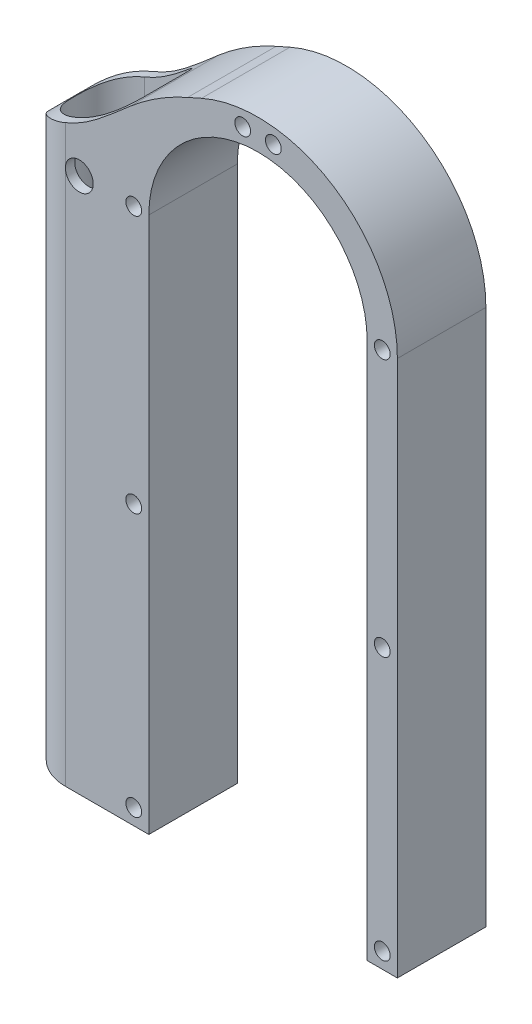
SolidWorks part; units mm, degrees
ref_plane "Front Plane" through (0, 0, 0) normal (0, 0, 1) x (1, 0, 0)
ref_plane "Top Plane" through (0, 0, 0) normal (0, 1, 0) x (1, 0, 0)
ref_plane "Right Plane" through (0, 0, 0) normal (1, 0, 0) x (0, 0, -1)
sketch "Sketch1" plane through (0, 0, 0) normal (0, 0, 1) x (1, 0, 0)
  line L0 (-179.0854, -18.7892) -> (-179.0854, 212.1883)
  line L1 (-119.0854, -18.7892) -> (-119.0854, 212.1883)
  line L2 (-172.5854, -18.7892) -> (-172.5854, 212.1883)
  line L3 (-125.5854, -18.7892) -> (-125.5854, 212.1883)
  arc A0 (-119.0854, 212.1883) -> (-179.0854, 212.1883) centre (-149.0854, 212.1883) ccw
  arc A1 (-179.0854, -18.7892) -> (-119.0854, -18.7892) centre (-149.0854, -18.7892) ccw
  arc A2 (-125.5854, 212.1883) -> (-172.5854, 212.1883) centre (-149.0854, 212.1883) ccw
  arc A3 (-172.5854, -18.7892) -> (-125.5854, -18.7892) centre (-149.0854, -18.7892) ccw
  dimension "D1" = 47
  dimension "D2" = 47
  dimension "D3" = 53.5
extrude "Boss-Extrude1" add sketch "Sketch1" along normal blind 19.05
sketch "Sketch2" plane through (0, 0, 19.05) normal (0, 0, 1) x (1, 0, 0)
  line L0 (-175.8354, 212.1883) -> (-175.8354, -18.7892) construction
  line L1 (-122.3354, 212.1883) -> (-122.3354, -18.7892) construction
  line L2 (-149.0854, 242.1883) -> (-149.0854, 231.9427) construction
  line L3 (-149.0854, -48.7892) -> (-149.0854, -37.4384) construction
  line L4 (-179.0854, 96.6996) -> (-118.7003, 96.6996) construction
  line L5 (-179.0854, 212.1883) -> (-179.0854, -18.7892) construction
  arc A0 (-122.3354, 212.1883) -> (-175.8354, 212.1883) centre (-149.0854, 212.1883) ccw construction
  arc A1 (-119.0854, 212.1883) -> (-179.0854, 212.1883) centre (-149.0854, 212.1883) ccw construction
  arc A2 (-125.5854, 212.1883) -> (-172.5854, 212.1883) centre (-149.0854, 212.1883) ccw construction
  arc A3 (-175.8354, -18.7892) -> (-122.3354, -18.7892) centre (-149.0854, -18.7892) ccw construction
  arc A4 (-179.0854, -18.7892) -> (-119.0854, -18.7892) centre (-149.0854, -18.7892) ccw construction
  circle A5 centre (-145.7854, 238.734) radius 1.7
  circle A7 centre (-122.3354, 212.1883) radius 1.7
  circle A8 centre (-152.4854, -45.3222) radius 1.7
  circle A9 centre (-168.0005, -37.7043) radius 1.7
  circle A10 centre (-175.8354, -18.7892) radius 1.7
  circle A11 centre (-175.8354, 212.1883) radius 1.7
  circle A13 centre (-145.6854, -45.3222) radius 1.7
  circle A14 centre (-175.8354, 100.0996) radius 1.7
  circle A15 centre (-175.8354, 93.2996) radius 1.7
  circle A16 centre (-122.3354, 100.0996) radius 1.7
  circle A17 centre (-122.3354, 93.2996) radius 1.7
  circle A19 centre (-122.3354, -18.7892) radius 1.7
  circle A20 centre (-130.1703, -37.7043) radius 1.7
  circle A25 centre (-175.8354, 156.6996) radius 1.7
  circle A26 centre (-122.3354, 156.6996) radius 1.7
  circle A29 centre (-175.8354, 66.6996) radius 1.7
  circle A30 centre (-122.3354, 66.6996) radius 1.7
  circle A31 centre (-175.8354, 36.6996) radius 1.7
  circle A32 centre (-122.3354, 36.6996) radius 1.7
  circle A33 centre (-175.8354, 6.6996) radius 1.7
  circle A34 centre (-122.3354, 6.6996) radius 1.7
  circle A35 centre (-152.3854, 238.734) radius 1.7
  point P35 (-149.0854, 212.1883)
  point P52 (-149.0854, -18.7892)
  dimension "D1" = 3.25
  dimension "D2" = 3.25
  dimension "D3" = 3.25
  dimension "D4" = 3.4
  dimension "D6" = 3.4
  dimension "D8" = 3.4
  dimension "D9" = 3.4
  dimension "D5" = 3.4
  dimension "D12" = 3.3
  dimension "D13" = 3.3
  dimension "D14" = 3.4
  dimension "D7" = 3.4
  dimension "D16" = 3.4
  dimension "D17" = 3.4
  dimension "D18" = 3.4
  dimension "D19" = 3.4
  dimension "D20" = 3.4
  dimension "D10" = 3.4
  dimension "D11" = 3.4
  dimension "D21" = 3.4
  dimension "D22" = 3.4
  dimension "D25" = 3.4
  dimension "D26" = 3.4
  dimension "D15" = 3.4
  dimension "D23" = 3.4
extrude "Cut-Extrude1" cut sketch "Sketch2" against normal through all
sketch "Sketch3" plane through (0, 0, 19.05) normal (0, 0, 1) x (1, 0, 0)
  line L1 (-149.0854, 96.6996) -> (-100.1673, 96.6996)
  line L2 (-100.1673, 96.6996) -> (-100.1673, -59.1719)
  line L3 (-100.1673, -59.1719) -> (-212.5278, -59.1719)
  line L4 (-212.5278, -59.1719) -> (-212.5278, 96.6996)
  line L5 (-149.0854, 96.6996) -> (-212.5278, 96.6996)
extrude "Cut-Extrude2" cut sketch "Sketch3" against normal through all
sketch "Sketch4" plane through (0, 96.6996, 0) normal (0, -1, 0) x (1, 0, 0)
  line L0 (-172.5854, 9.525) -> (-206.4878, 9.525) construction
  line L1 (-172.5854, 19.05) -> (-172.5854, 0) construction
  line L2 (-172.5854, 0) -> (-125.5854, 0) construction
  line L3 (-179.0854, 19.05) -> (-196.6522, 19.05)
  line L4 (-179.0854, 0) -> (-196.6522, 0)
  line L6 (-179.0854, 19.05) -> (-179.0854, 0)
  arc A1 (-196.6522, 19.05) -> (-196.6522, 0) centre (-187.0854, 9.525) ccw
  dimension "D1" = 27
extrude "Boss-Extrude2" add sketch "Sketch4" against normal blind 135
sketch "Sketch5" plane through (0, 0, 19.05) normal (0, 0, 1) x (1, 0, 0)
  line L0 (-179.0854, 231.6996) -> (-179.0854, 212.1883) construction
  line L1 (-179.0854, 231.6996) -> (-179.0854, 212.1883)
  line L2 (-179.0854, 231.6996) -> (-161.2502, 239.6113)
  arc A0 (-119.0854, 212.1883) -> (-179.0854, 212.1883) centre (-149.0854, 212.1883) ccw construction
  arc A1 (-161.2502, 239.6113) -> (-179.0854, 212.1883) centre (-149.0854, 212.1883) ccw
extrude "Boss-Extrude3" add sketch "Sketch5" against normal up to surface (19.05 mm away) up to face at (-120.6354, 100.0996, 0)
sketch "Sketch6" plane through (0, 0, 19.05) normal (0, 0, 1) x (1, 0, 0)
  line L0 (-200.5854, 231.6996) -> (-200.5854, 96.6996) construction
  line L1 (-196.6522, 231.6996) -> (-196.6522, 96.6996) construction
  line L2 (-170.1678, 235.6554) -> (-200.5854, 235.6554)
  line L3 (-200.5854, 235.6554) -> (-200.5854, 214.1406)
  line L5 (-161.2502, 239.6113) -> (-179.0854, 231.6996) construction
  spline S0 degree 3 poles (-170.1678, 235.6554) (-176.9003, 230.7465) (-186.9996, 219.5764) (-197.4753, 218.6619) (-200.5854, 214.1406) knots 0 0 0 0 0.54846 1 1 1 1
extrude "Cut-Extrude4" cut sketch "Sketch6" against normal through all
sketch "Sketch7" plane through (0, 96.6996, 0) normal (0, -1, 0) x (1, 0, 0)
  line L0 (-200.5854, 9.525) -> (-198.0854, 9.525) construction
  line L2 (-190.5854, 17.025) -> (-178.5854, 17.025)
  line L4 (-190.5854, 2.025) -> (-178.5854, 2.025)
  line L5 (-178.5854, 17.025) -> (-178.5854, 2.025)
  line L6 (-178.5854, 9.525) -> (-159.7434, 9.525) construction
  arc A3 (-196.6522, 19.05) -> (-196.6522, 0) centre (-187.0854, 9.525) ccw construction
  arc A4 (-190.5854, 17.025) -> (-190.5854, 2.025) centre (-190.5854, 9.525) ccw
  dimension "D1" = 15
  dimension "D2" = 3.5
  dimension "D4" = 22
extrude "Cut-Extrude5" cut sketch "Sketch7" against normal through all
fillet "Fillet2" radius 50 1 edges at (-170.1678, 235.6554, 9.525)
fillet "Fillet3" radius 10 2 edges at (-196.6522, 157.2144, 0) (-196.6522, 157.2144, 19.05)
fillet "Fillet4" radius 3 2 edges at (-178.5854, 162.7185, 17.025) (-178.5854, 162.7185, 2.025)
sketch "Sketch8" plane through (0, 0, 0) normal (0, 0, -1) x (-1, 0, 0)
  line L0 (190.553, 96.6996) -> (190.553, 220.4145) construction
  circle A0 centre (187.553, 211.996) radius 3
  dimension "D1" = 6
extrude "Cut-Extrude6" cut sketch "Sketch8" against normal through all
